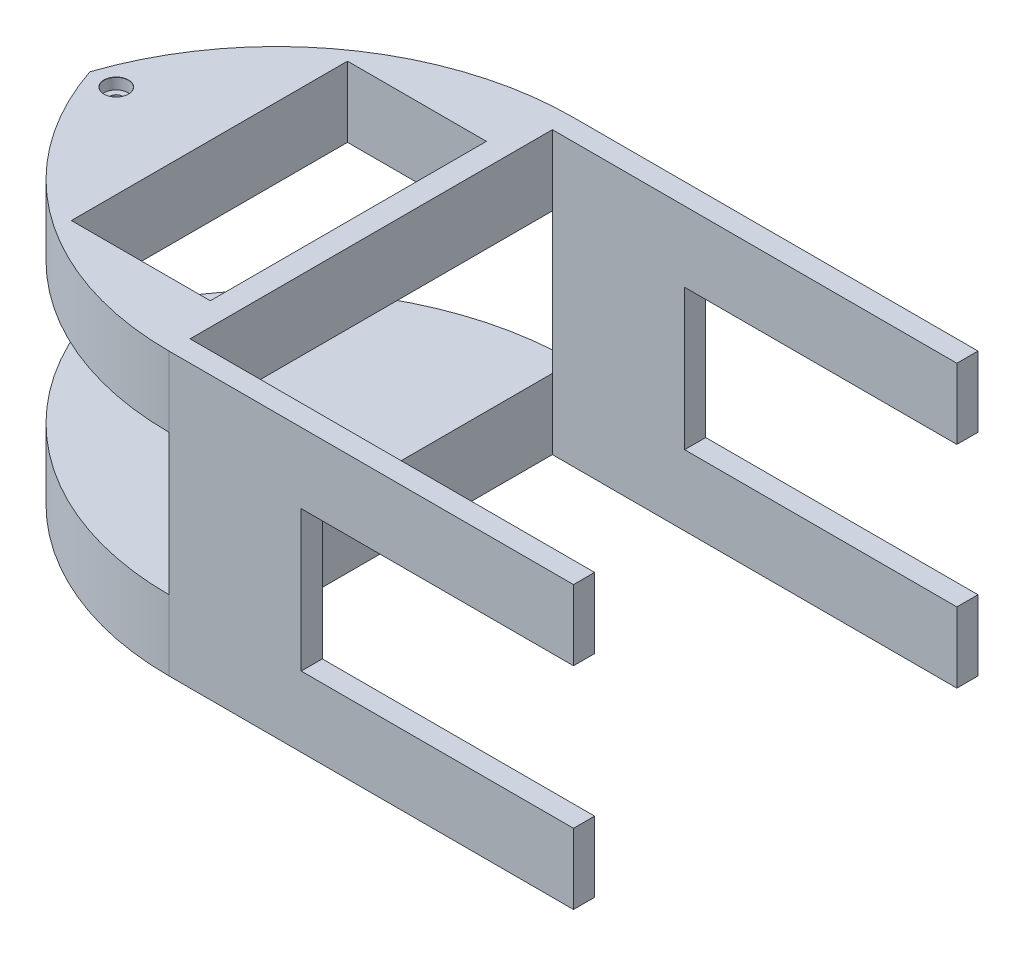
SolidWorks part; units mm, degrees
ref_plane "Front Plane" through (0, 0, 0) normal (0, 0, 1) x (1, 0, 0)
ref_plane "Top Plane" through (0, 0, 0) normal (0, 1, 0) x (1, 0, 0)
ref_plane "Right Plane" through (0, 0, 0) normal (1, 0, 0) x (0, 0, -1)
sketch "Sketch1" plane through (0, 0, 0) normal (0, 0, 1) x (1, 0, 0)
  line L0 (0, 0) -> (0, 20.32) construction
  line L1 (0, 20.32) -> (20.32, 20.32) construction
  line L2 (16.764, 0) -> (-16.764, 0) construction
  line L3 (20.32, 20.32) -> (0, 20.32)
  line L4 (20.32, 20.32) -> (20.32, 10.16)
  line L5 (20.32, 10.16) -> (0, 10.16)
  line L6 (0, 20.32) -> (0, 10.16)
  line L7 (20.32, 20.32) -> (0, 10.16) construction
  line L8 (20.32, 10.16) -> (0, 20.32) construction
  line L9 (0, 10.16) -> (-20.32, 10.16)
  line L10 (0, 10.16) -> (0, 20.32)
  line L11 (0, 20.32) -> (-20.32, 20.32)
  line L12 (-20.32, 10.16) -> (-20.32, 20.32)
  line L13 (0, 10.16) -> (-20.32, 20.32) construction
  line L14 (0, 20.32) -> (-20.32, 10.16) construction
  line L15 (0, 0) -> (0, -20.32) construction
  line L16 (20.32, -10.16) -> (0, -10.16)
  line L17 (0, -20.32) -> (0, -10.16)
  line L18 (20.32, -20.32) -> (0, -20.32)
  line L19 (20.32, -20.32) -> (20.32, -10.16)
  line L20 (0, -20.32) -> (-20.32, -20.32)
  line L21 (-20.32, -10.16) -> (-20.32, -20.32)
  line L22 (0, -10.16) -> (-20.32, -10.16)
  line L23 (0, -10.16) -> (0, -20.32)
  point P6 (10.16, 15.24)
  point P9 (-10.16, 15.24)
  dimension "D1" = 20.32
  dimension "D2" = 10.16
extrude "Boss-Extrude1" add sketch "Sketch1" along normal mid plane 58.42 contours L10 L9 L12 L11
mirror "Mirror1" about plane through (0, 0, 0) normal (1, 0, 0) of "Boss-Extrude1"
extrude "Boss-Extrude2" add sketch "Sketch1<4>" along normal mid plane 58.42 separate body contours L17 L22 L21 L20 | L18 L19 L16 L17 region at (10.16, -15.24, 0) region at (-10.16, -15.24, 0)
sketch "Sketch1<4>" plane through (0, 0, 0) normal (0, 0, 1) x (1, 0, 0) same geometry as "Sketch1"
sketch "Sketch5" plane through (20.32, 0, 0) normal (1, 0, 0) x (0, 0, -1)
  line L0 (-29.21, -20.32) -> (29.21, -20.32) construction
  line L1 (-29.21, 20.32) -> (-26.162, 20.32)
  line L2 (-29.21, 20.32) -> (-29.21, -20.32)
  line L3 (-29.21, -20.32) -> (-26.162, -20.32)
  line L4 (-26.162, 20.32) -> (-26.162, -20.32)
  line L5 (-29.21, 20.32) -> (-26.162, -20.32) construction
  line L6 (-29.21, -20.32) -> (-26.162, 20.32) construction
  line L7 (0, 22.352) -> (0, -22.352) construction
  line L8 (29.21, -20.32) -> (26.162, -20.32)
  line L9 (26.162, 20.32) -> (26.162, -20.32)
  line L10 (29.21, 20.32) -> (26.162, 20.32)
  line L11 (29.21, 20.32) -> (29.21, -20.32)
  line L12 (29.21, -20.32) -> (26.162, 20.32) construction
  line L13 (29.21, 20.32) -> (26.162, -20.32) construction
  point P4 (-27.686, 0)
  point P14 (27.686, 0)
  dimension "D1" = 3.048
extrude "Boss-Extrude4" add sketch "Sketch5" along normal blind 58.42
sketch "Sketch6" plane through (0, 20.32, 0) normal (0, 1, 0) x (1, 0, 0)
  line L0 (-20.32, 0) -> (-16.51, 0) construction
  line L2 (-20.32, -29.21) -> (-20.32, 29.21) construction
  point P8 (-16.51, 0)
  dimension "D1" = 3.81
hole_wizard "CBORE for M1.6 SHCS1" positions "Sketch7" profile "Sketch8" counterbore size "M1.6" standard "ANSI Metric" end condition through all
sketch "Sketch7" plane through (0, 20.32, 0) normal (0, 1, 0) x (1, 0, 0)
  point P0 (-16.51, 0)
sketch "Sketch8" plane through (-16.51, 20.32, 0) normal (1, 0, 0) x (0, 0, 1)
  line L0 (0, 0) -> (0, 40.64)
  line L1 (0, 40.64) -> (0.9, 40.64)
  line L3 (0.9, 40.64) -> (0.9, 1.6)
  line L4 (1.75, 1.6) -> (0.9, 1.6)
  line L5 (1.75, 1.6) -> (1.75, 0.025)
  line L6 (1.75, 0.025) -> (1.775, 0)
  line L7 (1.775, 0) -> (0, 0)
  line L8 (-1.75, 0.025) -> (-1.775, 0) construction
  line L11 (0, -6.35) -> (0, 107.95) construction
  dimension "Thru Hole Dia." = 1.8
  dimension "Thru Hole Depth" = 40.64
  dimension "C'Bore Dia." = 3.5
  dimension "C'Bore Depth" = 1.6
  dimension "Near C'Sink Dia." = 3.55
  dimension "Near C'Sink Angle" = 90
sketch "Sketch10" plane through (0, 0, 29.21) normal (0, 0, 1) x (1, 0, 0)
  line L0 (78.74, 20.32) -> (78.74, -20.32) construction
  line L1 (78.74, 10.16) -> (39.4164, 10.16)
  line L2 (78.74, 10.16) -> (78.74, -10.16)
  line L3 (78.74, -10.16) -> (39.4164, -10.16)
  line L4 (39.4164, 10.16) -> (39.4164, -10.16)
  line L5 (78.74, 10.16) -> (39.4164, -10.16) construction
  line L6 (78.74, -10.16) -> (39.4164, 10.16) construction
  line L7 (20.32, 0) -> (78.74, 0) construction
  line L8 (20.32, 10.16) -> (20.32, -10.16) construction
  point P4 (59.0782, 0)
  dimension "D1" = 10.16
  dimension "D2" = 10.16
extrude "Cut-Extrude2" cut sketch "Sketch10" against normal through all
sketch "Sketch12" plane through (0, 20.32, 0) normal (0, 1, 0) x (1, 0, 0)
  line L0 (-20.32, -29.21) -> (-20.32, 29.21)
  line L9 (-20.32, 29.21) -> (20.32, 29.21)
  line L10 (78.74, 29.21) -> (-20.32, 29.21) construction
  line L13 (-22.352, 0) -> (22.352, 0) construction
  line L15 (-20.32, -29.21) -> (20.32, -29.21)
  line L16 (20.32, -29.21) -> (-20.32, -29.21)
  arc A0 (-20.32, 0) -> (20.32, -29.21) centre (20.32, 13.6663) ccw
  arc A1 (-20.32, 0) -> (20.32, 29.21) centre (20.32, -13.6663) cw
  point P0 (0, 0)
  line M13 (78.74, 29.21) -> (-20.32, 29.21)
  line M14 (-20.32, 29.21) -> (-20.32, -29.21)
  line M15 (-20.32, -29.21) -> (78.74, -29.21)
extrude "Cut-Extrude4" cut sketch "Sketch12" against normal blind 58.42 contours M13 M14 | L0 M15 region at (-10.9662, 20.32, -21.3894) region at (-10.9662, 20.32, 21.3894)
sketch "Sketch13" plane through (0, 20.32, 0) normal (0, 1, 0) x (1, 0, 0)
  line L0 (-6.35, 0) -> (20.32, 0) construction
  line L2 (20.32, -26.162) -> (20.32, 26.162) construction
  line L3 (78.74, -26.162) -> (78.74, -29.21) construction
  line L4 (-3.048, -19.939) -> (17.018, -19.939)
  line L5 (-3.048, -19.939) -> (-3.048, 19.939)
  line L6 (-3.048, 19.939) -> (17.018, 19.939)
  line L7 (17.018, -19.939) -> (17.018, 19.939)
  line L8 (-3.048, -19.939) -> (17.018, 19.939) construction
  line L9 (-3.048, 19.939) -> (17.018, -19.939) construction
  point P5 (6.985, 0)
  dimension "D1" = 39.878
  dimension "D2" = 20.066
  dimension "D3" = 61.722
extrude "Cut-Extrude5" cut sketch "Sketch13" against normal up to next
